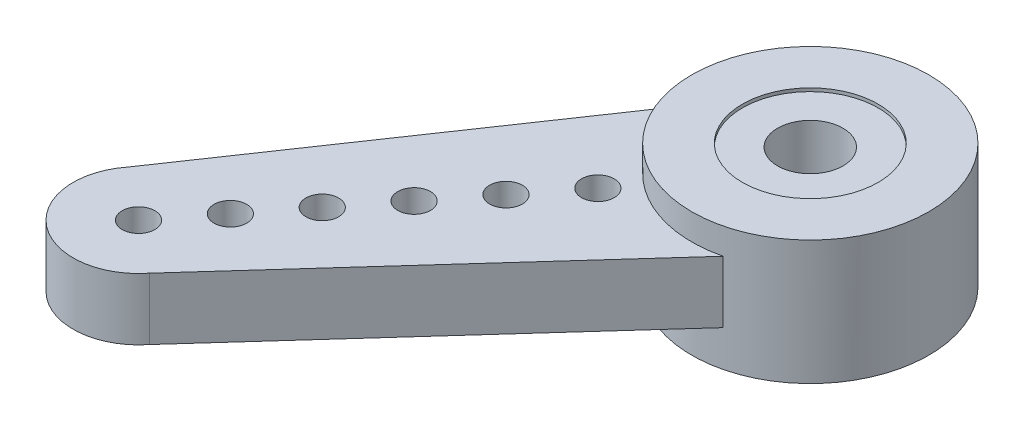
SolidWorks part; units mm, degrees
note: The reader was unsure of these and kept them because the rebuilt part matched: shared geometry of "Sketch1<2>".
ref_plane "Front Plane" through (0, 0, 0) normal (0, 0, 1) x (1, 0, 0)
ref_plane "Top Plane" through (0, 0, 0) normal (0, 1, 0) x (1, 0, 0)
ref_plane "Right Plane" through (0, 0, 0) normal (1, 0, 0) x (0, 0, -1)
sketch "Sketch1" plane through (0, 0, 0) normal (0, 1, 0) x (1, 0, 0)
  circle A0 centre (0, 0) radius 3.625
  circle A1 centre (0, 0) radius 2.075
extrude "Boss-Extrude1" add sketch "Sketch1" along normal blind 2.41
sketch "Sketch2" plane through (0, 2.41, 0) normal (0, 1, 0) x (1, 0, 0)
  line L4 (-10.6055, -10.2672) -> (-3.625, 0)
  line L5 (-7.4595, -12.7376) -> (0.8596, -3.5216)
  circle A0 centre (0, 0) radius 1
  arc A1 (0.8596, -3.5216) -> (-3.625, 0) centre (0, 0) ccw
  arc A2 (-10.6055, -10.2672) -> (-7.4595, -12.7376) centre (-9.0325, -11.5024) ccw
  circle A4 centre (-9.0325, -11.5024) radius 0.5
  circle A5 centre (-7.7973, -9.9294) radius 0.5
  circle A6 centre (-6.5621, -8.3564) radius 0.5
  circle A7 centre (-5.3268, -6.7835) radius 0.5
  circle A8 centre (-4.0916, -5.2105) radius 0.5
  circle A9 centre (-2.8564, -3.6375) radius 0.5
  point P7 (-2.2388, -2.851)
extrude "Boss-Extrude3" add sketch "Sketch2" along normal blind 1.89
extrude "Boss-Extrude4" add sketch "Sketch1<2>" along normal blind 0.8 from surface at 4.3 starting at face at (-4.0916, 4.3, 5.7105)
sketch "Sketch1<2>" plane through (0, 0, 0) normal (0, 1, 0) x (1, 0, 0) same geometry as "Sketch1"
sketch "Sketch3" plane through (0, 0, 0) normal (0, -1, 0) x (1, 0, 0)
  circle A0 centre (0, 0) radius 2.075 construction
  circle A1 centre (0, 0) radius 3.625
  circle A2 centre (0, 0) radius 3.625
  circle A3 centre (0, 0) radius 2.075
  dimension "D1" = 0
extrude "Cut-Extrude1" cut sketch "Sketch3" against normal blind 1.3
sketch "Sketch4" plane through (0, 4.3, 0) normal (0, 1, 0) x (1, 0, 0)
  circle A0 centre (0, 0) radius 1 construction
  circle A1 centre (0, 0) radius 2.075
  circle A2 centre (0, 0) radius 2.075
  circle A3 centre (0, 0) radius 1
  dimension "D1" = 0
extrude "Boss-Extrude5" add sketch "Sketch4" along normal blind 0.7
sketch "Sketch5" plane through (0, 2.41, 0) normal (0, -1, 0) x (1, 0, 0)
  circle A0 centre (0, 0) radius 1 construction
  circle A1 centre (0, 0) radius 2.075
  circle A2 centre (0, 0) radius 2.075
  circle A3 centre (0, 0) radius 1
  dimension "D1" = 0
extrude "Cut-Extrude2" cut sketch "Sketch5" against normal blind 1
